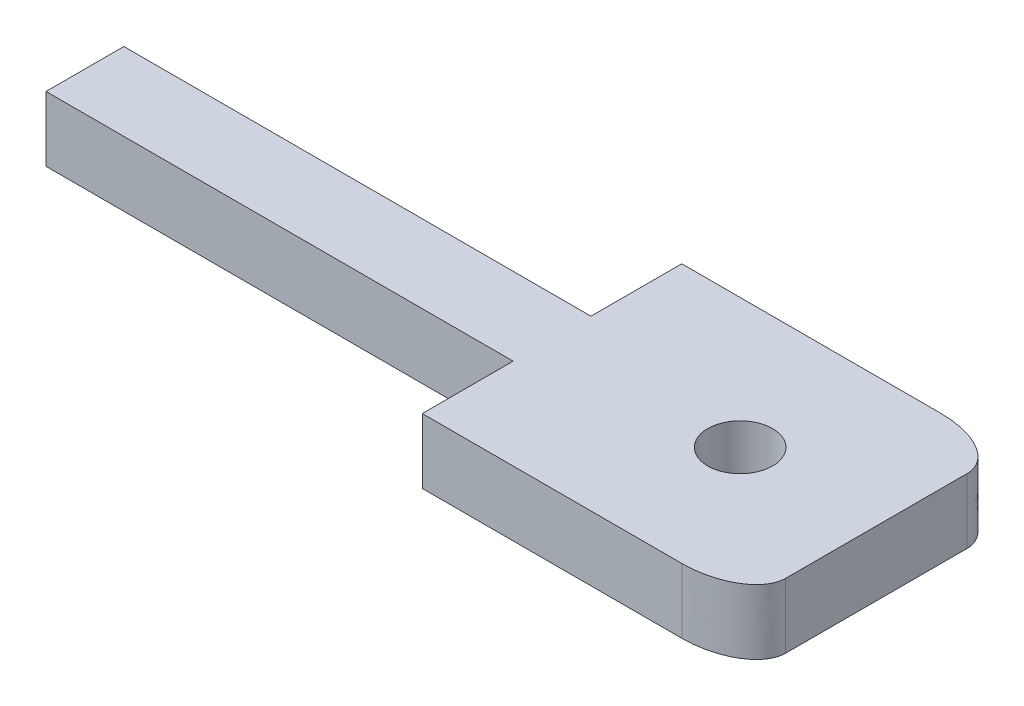
SolidWorks part; units mm, degrees
ref_plane "Front Plane" through (0, 0, 0) normal (0, 0, 1) x (1, 0, 0)
ref_plane "Top Plane" through (0, 0, 0) normal (0, 1, 0) x (1, 0, 0)
ref_plane "Right Plane" through (0, 0, 0) normal (1, 0, 0) x (0, 0, -1)
sketch "Sketch1" plane through (0, 0, 0) normal (0, 0, 1) x (1, 0, 0)
  line L0 (6.5, 2.5) -> (12.5, 2.5)
  line L1 (-12.5, -2.5) -> (12.5, -2.5)
  line L2 (-12.5, -2.5) -> (-12.5, 2.5)
  line L3 (-12.5, 2.5) -> (6.5, 2.5)
  line L4 (12.5, -2.5) -> (12.5, 2.5)
  line L5 (-12.5, -2.5) -> (12.5, 2.5) construction
  line L6 (-12.5, 2.5) -> (12.5, -2.5) construction
  point P0 (0, 0)
  dimension "D1" = 25
  dimension "D2" = 5
extrude "Boss-Extrude1" add sketch "Sketch1" along normal blind 20
sketch "Sketch2" plane through (0, 2.5, 0) normal (0, 1, 0) x (1, 0, 0)
  line L24 (12.5, -20) -> (12.5, 0) construction
  line L32 (12.5, -20) -> (-12.5, -20) construction
  line L33 (-10.5, -10) -> (-1.5, -10) construction
  line L34 (12.5, 0) -> (-12.5, 0) construction
  circle A6 centre (2, -10) radius 2.5
  dimension "D7" = 10.5
  dimension "D6" = 5
extrude "Cut-Extrude2" cut sketch "Sketch2" against normal through all both and the other way through all contours A6 L33 | L33 A6
fillet "Fillet1" radius 5 2 edges at (12.5, 0, 20) (12.5, 0, 0) second distance 3 first distance on face at (0, 0, 20) first distance on face at (0, 0, 0)
sketch "Sketch3" plane through (0, 0, 0) normal (0, 1, 0) x (1, 0, 0)
  line L0 (-12.5, -20) -> (-12.5, 0) construction
  line L1 (-12.5, -7) -> (-48.5, -7)
  line L2 (-12.5, -7) -> (-12.5, -13)
  line L3 (-12.5, -13) -> (-48.5, -13)
  line L4 (-48.5, -7) -> (-48.5, -13)
  line L5 (-200010.5, -10) -> (199998.5, -10) construction
  line L6 (-200010.5, -10) -> (199998.5, -10) construction
  line L7 (-76.602, -10) -> (34.8945, -10) construction
  point P10 (0, 0)
  dimension "D1" = 6
  dimension "D2" = 36
extrude "Boss-Extrude2" add sketch "Sketch3" along normal up to surface and the other way up to surface up to face at (2, 2.5, 7.5) other way up to face at (2, -2.5, 12.5)
